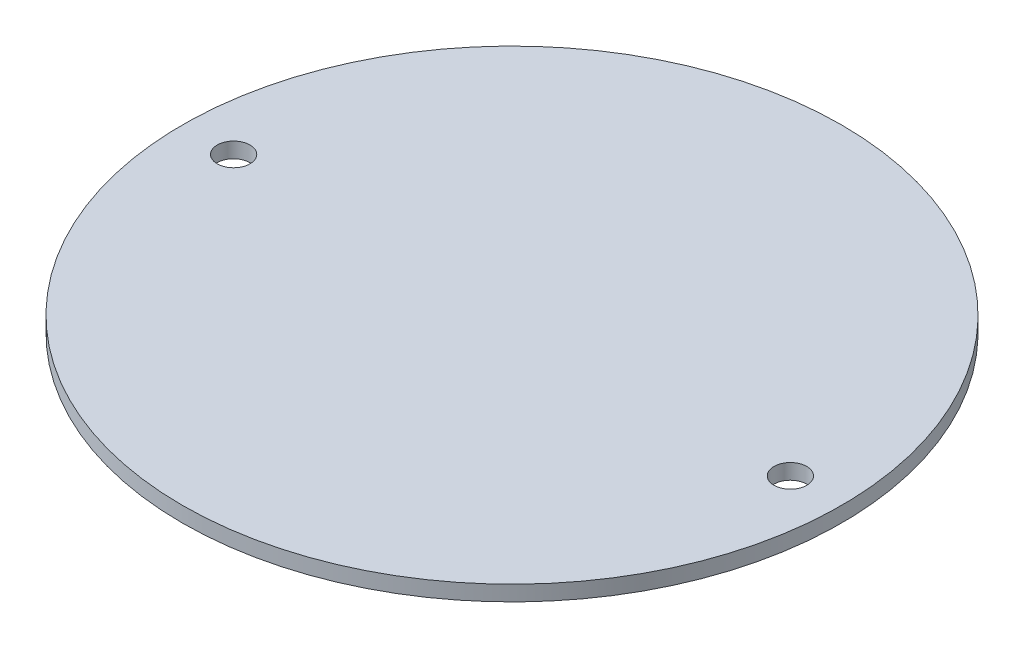
SolidWorks part; units mm, degrees
ref_plane "Front Plane" through (0, 0, 0) normal (0, 0, 1) x (1, 0, 0)
ref_plane "Top Plane" through (0, 0, 0) normal (0, 1, 0) x (1, 0, 0)
ref_plane "Right Plane" through (0, 0, 0) normal (1, 0, 0) x (0, 0, -1)
sketch "Sketch1" plane through (0, 0, 0) normal (0, 1, 0) x (1, 0, 0)
  circle A0 centre (0, 0) radius 64.4
  dimension "Diameter" = 128.8
extrude "Boss-Extrude1" add sketch "Sketch1" along normal mid plane 3
sketch "Sketch2" plane through (0, 1.5, 0) normal (0, 1, 0) x (1, 0, 0)
  line L0 (-54.4, 0) -> (54.4, 0) construction
  point P2 (0, 0)
  dimension "RodDistance" = 108.8
hole_wizard "M6 Clearance Hole1" positions "Sketch3" profile "Sketch4" hole size "M6" standard "ANSI Metric" end condition up to next
sketch "Sketch3" plane through (0, 1.5, 0) normal (0, 1, 0) x (1, 0, 0)
  point P0 (-54.4, 0)
  point P3 (54.4, 0)
sketch "Sketch4" plane through (-54.4, 1.5, 0) normal (1, 0, 0) x (0, 0, 1)
  line L0 (0, 0) -> (0, 3)
  line L1 (0, 3) -> (3.2, 3)
  line L2 (3.2, 3) -> (3.2, 0)
  line L5 (3.2, 0) -> (0, 0)
  line L11 (0, -6.35) -> (0, 107.95) construction
  dimension "Thru Hole Dia." = 6.4
  dimension "Thru Hole Depth" = 3
